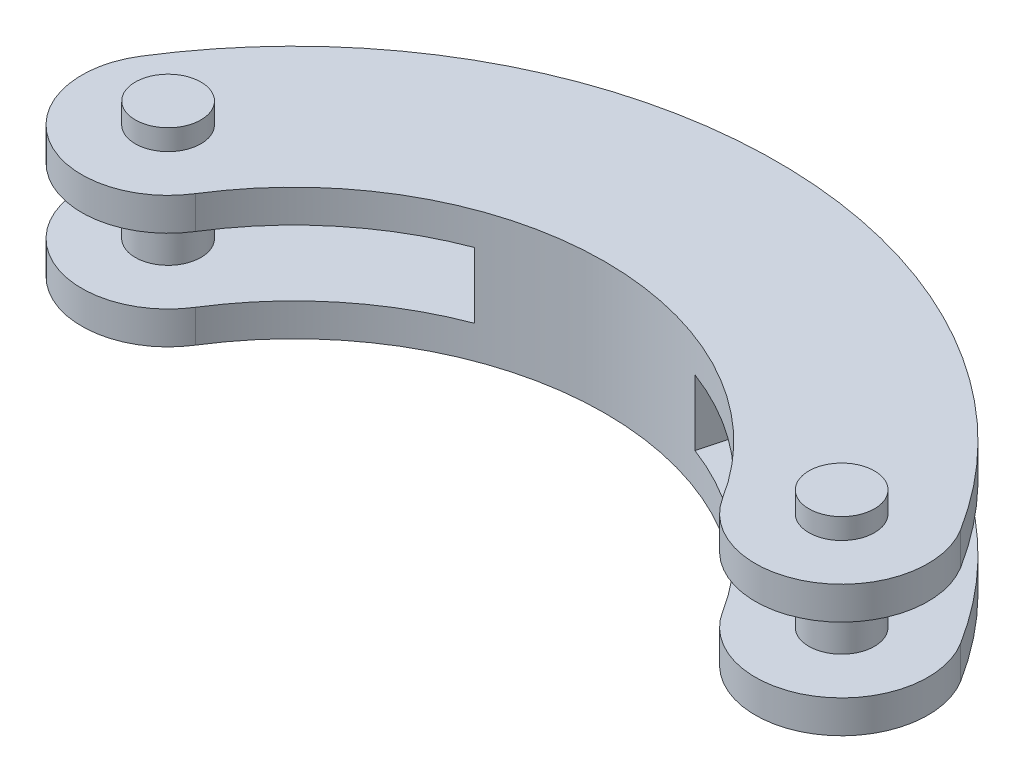
SolidWorks part; units mm, degrees
ref_plane "Front Plane" through (0, 0, 0) normal (0, 0, 1) x (1, 0, 0)
ref_plane "Top Plane" through (0, 0, 0) normal (0, 1, 0) x (1, 0, 0)
ref_plane "Right Plane" through (0, 0, 0) normal (1, 0, 0) x (0, 0, -1)
sketch "Sketch1" plane through (0, 0, 0) normal (0, 1, 0) x (1, 0, 0)
  line L0 (-97.5, -53.9543) -> (97.5, -53.9543) construction
  arc A0 (-97.5, -53.9543) -> (97.5, -53.9543) centre (0, -115.0725) cw construction
  arc A1 (118.6823, -40.6761) -> (-118.6823, -40.6761) centre (0, -115.0725) ccw
  arc A2 (76.3177, -67.2325) -> (-76.3177, -67.2325) centre (0, -115.0725) ccw
  arc A3 (76.3177, -67.2325) -> (118.6823, -40.6761) centre (97.5, -53.9543) ccw
  arc A4 (-118.6823, -40.6761) -> (-76.3177, -67.2325) centre (-97.5, -53.9543) ccw
  point P3 (0, 0)
  dimension "D2" = 25
  dimension "D1" = 195
extrude "Boss-Extrude1" add sketch "Sketch1" along normal blind 9.5
sketch "Sketch2" plane through (0, 9.5, 0) normal (0, 1, 0) x (1, 0, 0)
  line L0 (0, -150) -> (0, 89.0407) construction
  line L1 (0, -150) -> (-44.9097, 17.6054)
  line L2 (0, -150) -> (44.9097, 17.6054)
  arc A0 (118.6823, -40.6761) -> (-118.6823, -40.6761) centre (0, -115.0725) ccw construction
  arc M4 (118.6823, -40.6761) -> (-118.6823, -40.6761) centre (0, -115.0725) ccw
  arc M6 (-76.3177, -67.2325) -> (76.3177, -67.2325) centre (0, -115.0725) cw
  dimension "D1" = 150
  dimension "D2" = 15
extrude "Boss-Extrude2" add sketch "Sketch2" along normal blind 19 contours L0 L1 M6 M4 | L0 L2 M6 M4 region at (-19.5802, 9.5, 0.8349) region at (19.5802, 9.5, 0.8349)
sketch "Sketch3" plane through (0, 28.5, 0) normal (0, 1, 0) x (1, 0, 0)
  line L2 (31.9266, -30.8481) -> (44.9097, 17.6054)
  line L3 (-44.9097, 17.6054) -> (-31.9266, -30.8481)
  line L4 (31.9266, -30.8481) -> (44.9097, 17.6054)
  line L5 (-44.9097, 17.6054) -> (-31.9266, -30.8481)
  arc A2 (31.9266, -30.8481) -> (-31.9266, -30.8481) centre (0, -115.0725) ccw
  arc A3 (44.9097, 17.6054) -> (-44.9097, 17.6054) centre (0, -115.0725) ccw
  arc A4 (31.9266, -30.8481) -> (-31.9266, -30.8481) centre (0, -115.0725) ccw
  arc A5 (44.9097, 17.6054) -> (-44.9097, 17.6054) centre (0, -115.0725) ccw
  arc A8 (76.3177, -67.2325) -> (118.6823, -40.6761) centre (97.5, -53.9543) ccw
  arc A9 (76.3177, -67.2325) -> (-76.3177, -67.2325) centre (0, -115.0725) ccw
  arc A10 (-118.6823, -40.6761) -> (-76.3177, -67.2325) centre (-97.5, -53.9543) ccw
  arc A11 (118.6823, -40.6761) -> (-118.6823, -40.6761) centre (0, -115.0725) ccw
  arc A12 (76.3177, -67.2325) -> (118.6823, -40.6761) centre (97.5, -53.9543) ccw
  arc A13 (76.3177, -67.2325) -> (-76.3177, -67.2325) centre (0, -115.0725) ccw
  arc A14 (-118.6823, -40.6761) -> (-76.3177, -67.2325) centre (-97.5, -53.9543) ccw
  arc A15 (118.6823, -40.6761) -> (-118.6823, -40.6761) centre (0, -115.0725) ccw
  arc M9 (-31.9266, -30.8481) -> (31.9266, -30.8481) centre (0, -115.0725) cw
  line M10 (31.9266, -30.8481) -> (44.9097, 17.6054)
  arc M11 (44.9097, 17.6054) -> (-44.9097, 17.6054) centre (0, -115.0725) ccw
  line M12 (-44.9097, 17.6054) -> (-31.9266, -30.8481)
  dimension "D1" = 0
  dimension "D2" = 0
extrude "Boss-Extrude3" add sketch "Sketch3" along normal blind 9.5 contours A15 A14 A13 M12 | M12 M9 M10 M11 | A12 A15 A13 M10 region at (0, 28.5, 0.8349) region at (78.1584, 28.5, 32.9882) region at (-78.1584, 28.5, 32.9882)
sketch "Sketch4" plane through (0, 38, 0) normal (0, 1, 0) x (1, 0, 0)
  circle A0 centre (-97.5, -53.9543) radius 9.5
  circle A1 centre (97.5, -53.9543) radius 9.5
  dimension "D1" = 19
  dimension "D2" = 19
extrude "Cut-Extrude1" cut sketch "Sketch4" against normal through all
extrude "Boss-Extrude4" add sketch "Sketch4<2>" against normal blind 50 from offset 6
sketch "Sketch4<2>" plane through (0, 38, 0) normal (0, 1, 0) x (1, 0, 0) same geometry as "Sketch4"
